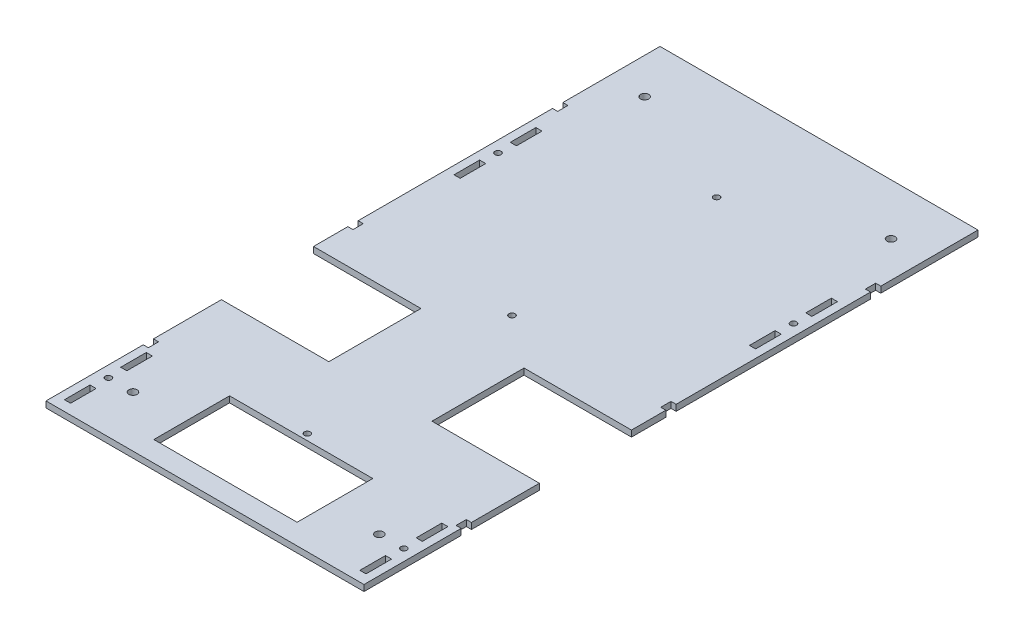
SolidWorks part; units mm, degrees
material "PMMA"
ref_plane "Front Plane" through (0, 0, 0) normal (0, 0, 1) x (1, 0, 0)
ref_plane "Top Plane" through (0, 0, 0) normal (0, 1, 0) x (1, 0, 0)
ref_plane "Right Plane" through (0, 0, 0) normal (1, 0, 0) x (0, 0, -1)
sketch "Schizzo1" plane through (0, 0, 0) normal (0, 1, 0) x (1, 0, 0)
  line L0 (-80.18, 150) -> (80.18, -150) construction
  line L1 (-80.18, 150) -> (80.18, 150)
  line L2 (-80.18, 150) -> (-80.18, -150)
  line L3 (-80.18, -150) -> (80.18, -150)
  line L4 (80.18, 150) -> (80.18, -150)
  point P4 (0, 0)
  dimension "D1" = 300
  dimension "D2" = 160.36
extrude "Estrusione-Estrusione1" add sketch "Schizzo1" along normal blind 3
sketch "Schizzo3" plane through (0, 0, 0) normal (0, 1, 0) x (1, 0, 0)
  line L0 (-80.18, 0) -> (80.18, 0) construction
  line L1 (-80.18, 150) -> (-80.18, -150) construction
  line L2 (0, 0) -> (0, -100) construction
  line L3 (0, 150) -> (0, -150) construction
  line L4 (80.18, 150) -> (-80.18, 150) construction
  line L5 (-80.18, -150) -> (80.18, -150) construction
  line L6 (0, 0) -> (0, 100) construction
  line L7 (-75.18, -97.5) -> (-80.18, -97.5)
  line L8 (-75.18, -2.5) -> (-80.18, -2.5)
  line L9 (-75.18, -2.5) -> (-75.18, 2.5)
  line L10 (-75.18, 2.5) -> (-80.18, 2.5)
  line L11 (-80.18, -2.5) -> (-80.18, 2.5)
  line L12 (-80.18, -102.5) -> (-80.18, -97.5)
  line L13 (-75.18, -102.5) -> (-80.18, -102.5)
  line L14 (-75.18, -102.5) -> (-75.18, -97.5)
  line L15 (-75.18, 2.5) -> (-75.18, -97.5) construction
  line L16 (-75.18, 97.5) -> (-80.18, 97.5)
  line L17 (-80.18, 97.5) -> (-80.18, 102.5)
  line L18 (-75.18, 102.5) -> (-80.18, 102.5)
  line L19 (-75.18, 97.5) -> (-75.18, 102.5)
  line L20 (-75.18, -2.5) -> (-75.18, 97.5) construction
  line L21 (75.18, -102.5) -> (75.18, -97.5)
  line L22 (75.18, -97.5) -> (80.18, -97.5)
  line L23 (80.18, -102.5) -> (80.18, -97.5)
  line L24 (75.18, -102.5) -> (80.18, -102.5)
  line L25 (75.18, -2.5) -> (75.18, 2.5)
  line L26 (75.18, 2.5) -> (80.18, 2.5)
  line L27 (80.18, -2.5) -> (80.18, 2.5)
  line L28 (75.18, -2.5) -> (80.18, -2.5)
  line L29 (75.18, 97.5) -> (75.18, 102.5)
  line L30 (75.18, 102.5) -> (80.18, 102.5)
  line L31 (80.18, 97.5) -> (80.18, 102.5)
  line L32 (75.18, 97.5) -> (80.18, 97.5)
  line L33 (-80.18, 150) -> (-80.18, -150) construction
  line L34 (-80.18, -19.3) -> (-25.18, -19.3)
  line L35 (-80.18, -19.3) -> (-80.18, -64.3)
  line L36 (-80.18, -64.3) -> (-25.18, -64.3)
  line L37 (-25.18, -19.3) -> (-25.18, -64.3)
  line L38 (80.18, -19.3) -> (80.18, -64.3)
  line L39 (80.18, -64.3) -> (25.18, -64.3)
  line L40 (25.18, -19.3) -> (25.18, -64.3)
  line L41 (80.18, -19.3) -> (25.18, -19.3)
  line L54 (80.18, -150) -> (80.18, 150) construction
  circle A0 centre (0, 0) radius 1.5
  circle A1 centre (0, -100) radius 1.5
  circle A2 centre (0, 100) radius 1.5
  circle A8 centre (-5.0427, -204.0432) radius 1.5
  point P24 (-80.18, 0)
  dimension "D1" = 3
  dimension "D2" = 100
  dimension "D4" = 100
  dimension "D5" = 5
  dimension "D6" = 5
  dimension "D7" = 100
  dimension "D9" = 100
  dimension "D11" = 55
  dimension "D12" = 45
  dimension "D13" = 16.8
  dimension "D10" = 2
extrude "Taglio-Estrusione1" cut sketch "Schizzo3" along direction (0, 1, 0) on the side of the normal through all
sketch "Schizzo4" plane through (0, 0, 0) normal (0, 1, 0) x (1, 0, 0)
  line L0 (-80.18, -102.5) -> (-80.18, -150) construction
  line L1 (-80.18, -150) -> (80.18, -150) construction
  line L2 (0, -150) -> (0, 150) construction
  line L3 (80.18, 150) -> (-80.18, 150) construction
  line L4 (75.18, 0) -> (-75.18, 0) construction
  line L5 (75.18, 2.5) -> (75.18, -2.5) construction
  line L6 (-75.18, -2.5) -> (-75.18, 2.5) construction
  circle A0 centre (-60.18, -125) radius 2
  circle A1 centre (60.18, -125) radius 2
  circle A2 centre (-60.18, 125) radius 2
  circle A3 centre (60.18, 125) radius 2
  dimension "D1" = 4
  dimension "D2" = 20
  dimension "D3" = 25
  dimension "D4" = 250
  dimension "D5" = 120.36
extrude "Taglio-Estrusione2" cut sketch "Schizzo4" along direction (0, 1, 0) on the side of the normal through all
sketch "Schizzo5" plane through (0, 0, 0) normal (0, 1, 0) x (1, 0, 0)
  line L0 (0, -150) -> (0, 150) construction
  line L1 (-80.18, -150) -> (80.18, -150) construction
  line L2 (80.18, 150) -> (-80.18, 150) construction
  line L3 (-80.18, -125) -> (80.18, -125) construction
  line L5 (80.18, -150) -> (80.18, -102.5) construction
  line L6 (-80.18, 65.35) -> (80.18, 65.35) construction
  line L7 (-80.18, 97.5) -> (-80.18, 2.5) construction
  line L8 (80.18, 2.5) -> (80.18, 97.5) construction
  line L10 (-80.18, 150) -> (-80.18, -19.3) construction
  line L11 (-80.18, -64.3) -> (-80.18, -150) construction
  line L12 (72.18, 72.85) -> (72.18, 57.85) construction
  line L13 (70.68, 85.35) -> (73.68, 85.35)
  line L14 (70.68, 85.35) -> (70.68, 72.85)
  line L15 (70.68, 72.85) -> (73.68, 72.85)
  line L16 (73.68, 85.35) -> (73.68, 72.85)
  line L17 (70.68, 57.85) -> (73.68, 57.85)
  line L18 (70.68, 57.85) -> (70.68, 45.35)
  line L19 (70.68, 45.35) -> (73.68, 45.35)
  line L20 (73.68, 57.85) -> (73.68, 45.35)
  line L21 (-70.68, 57.85) -> (-73.68, 57.85)
  line L22 (-70.68, 57.85) -> (-70.68, 45.35)
  line L23 (-70.68, 45.35) -> (-73.68, 45.35)
  line L24 (-73.68, 57.85) -> (-73.68, 45.35)
  line L25 (-70.68, 85.35) -> (-73.68, 85.35)
  line L26 (-70.68, 85.35) -> (-70.68, 72.85)
  line L27 (-70.68, 72.85) -> (-73.68, 72.85)
  line L28 (-73.68, 85.35) -> (-73.68, 72.85)
  line L29 (72.18, -117.5) -> (72.18, -132.5) construction
  line L30 (70.68, -105) -> (73.68, -105)
  line L31 (70.68, -105) -> (70.68, -117.5)
  line L32 (70.68, -117.5) -> (73.68, -117.5)
  line L33 (73.68, -105) -> (73.68, -117.5)
  line L34 (70.68, -132.5) -> (73.68, -132.5)
  line L35 (70.68, -132.5) -> (70.68, -145)
  line L36 (70.68, -145) -> (73.68, -145)
  line L37 (73.68, -132.5) -> (73.68, -145)
  line L38 (-70.68, -105) -> (-73.68, -105)
  line L39 (-70.68, -105) -> (-70.68, -117.5)
  line L40 (-70.68, -117.5) -> (-73.68, -117.5)
  line L41 (-73.68, -105) -> (-73.68, -117.5)
  line L42 (-70.68, -132.5) -> (-73.68, -132.5)
  line L43 (-70.68, -132.5) -> (-70.68, -145)
  line L44 (-70.68, -145) -> (-73.68, -145)
  line L45 (-73.68, -132.5) -> (-73.68, -145)
  circle A0 centre (72.18, 65.35) radius 1.5
  circle A1 centre (-72.18, 65.35) radius 1.5
  circle A2 centre (72.18, -125) radius 1.5
  circle A3 centre (-72.18, -125) radius 1.5
  dimension "D4" = 3
  dimension "D9" = 3
  dimension "D1" = 12.5
  dimension "D2" = 3
  dimension "D3" = 40
  dimension "D5" = 6.5
  dimension "D6" = 12.5
  dimension "D7" = 3
  dimension "D8" = 40
  dimension "D10" = 6.5
  dimension "D11" = 25
extrude "Taglio-Estrusione3" cut sketch "Schizzo5" along direction (0, 1, 0) on the side of the normal through all
sketch "Schizzo6" plane through (0, 0, 0) normal (0, 1, 0) x (1, 0, 0)
  line L1 (35, -140) -> (-35, -140)
  line L2 (35, -140) -> (35, -103)
  line L3 (35, -103) -> (-35, -103)
  line L4 (-35, -140) -> (-35, -103)
  line L6 (-80.18, -150) -> (80.18, -150) construction
  dimension "D1" = 37
  dimension "D2" = 70
  dimension "D3" = 35
  dimension "D4" = 10
extrude "Taglio-Estrusione4" cut sketch "Schizzo6" along direction (0, 1, 0) on the side of the normal through all
sketch "Schizzo7" plane through (0, 3, 0) normal (0, 1, 0) x (1, 0, 0)
  line L0 (-75.18, 102.5) -> (-80.18, 102.5) construction
  line L1 (-80.18, 150) -> (-77.68, 150)
  line L2 (-80.18, 150) -> (-80.18, 102.5)
  line L3 (-80.18, 102.5) -> (-77.68, 102.5)
  line L4 (-77.68, 150) -> (-77.68, 102.5)
  line L5 (-75.18, 2.5) -> (-80.18, 2.5) construction
  line L6 (-77.68, 2.5) -> (-80.18, 2.5)
  line L7 (-77.68, 2.5) -> (-77.68, 97.5)
  line L8 (-77.68, 97.5) -> (-80.18, 97.5)
  line L9 (-80.18, 2.5) -> (-80.18, 97.5)
  line L10 (-80.18, -2.5) -> (-75.18, -2.5) construction
  line L11 (-77.68, -2.5) -> (-80.18, -2.5)
  line L12 (-77.68, -2.5) -> (-77.68, -19.3)
  line L13 (-77.68, -19.3) -> (-80.18, -19.3)
  line L14 (-80.18, -2.5) -> (-80.18, -19.3)
  line L15 (-75.18, -97.5) -> (-80.18, -97.5) construction
  line L16 (-80.18, -64.3) -> (-77.68, -64.3)
  line L17 (-80.18, -64.3) -> (-80.18, -97.5)
  line L18 (-80.18, -97.5) -> (-77.68, -97.5)
  line L19 (-77.68, -64.3) -> (-77.68, -97.5)
  line L20 (-80.18, -150) -> (80.18, -150) construction
  line L21 (-77.68, -150) -> (-80.18, -150)
  line L22 (-77.68, -150) -> (-77.68, -102.5)
  line L23 (-77.68, -102.5) -> (-80.18, -102.5)
  line L24 (-80.18, -150) -> (-80.18, -102.5)
  line L25 (75.18, -102.5) -> (80.18, -102.5) construction
  line L26 (80.18, -150) -> (77.68, -150)
  line L27 (80.18, -150) -> (80.18, -102.5)
  line L28 (80.18, -102.5) -> (77.68, -102.5)
  line L29 (77.68, -150) -> (77.68, -102.5)
  line L30 (80.18, -97.5) -> (75.18, -97.5) construction
  line L31 (80.18, -64.3) -> (77.68, -64.3)
  line L32 (80.18, -64.3) -> (80.18, -97.5)
  line L33 (80.18, -97.5) -> (77.68, -97.5)
  line L34 (77.68, -64.3) -> (77.68, -97.5)
  line L35 (75.18, -2.5) -> (80.18, -2.5) construction
  line L36 (80.18, -19.3) -> (77.68, -19.3)
  line L37 (80.18, -19.3) -> (80.18, -2.5)
  line L38 (80.18, -2.5) -> (77.68, -2.5)
  line L39 (77.68, -19.3) -> (77.68, -2.5)
  line L40 (80.18, 102.5) -> (75.18, 102.5) construction
  line L41 (80.18, 150) -> (77.68, 150)
  line L42 (80.18, 150) -> (80.18, 102.5)
  line L43 (80.18, 102.5) -> (77.68, 102.5)
  line L44 (77.68, 150) -> (77.68, 102.5)
  line L45 (80.18, 2.5) -> (75.18, 2.5) construction
  line L46 (80.18, 97.5) -> (77.68, 97.5)
  line L47 (80.18, 97.5) -> (80.18, 2.5)
  line L48 (80.18, 2.5) -> (77.68, 2.5)
  line L49 (77.68, 97.5) -> (77.68, 2.5)
extrude "Taglio-Estrusione5" cut sketch "Schizzo7" against normal through all
equation "\"Thickness2\"=12"
equation "\"Thickness3\"=3"
equation "\"D1@Estrusione-Estrusione1\"=\"Thickness3\""
equation "\"D5@Schizzo3\"=\"Thickness5\""
equation "\"D6@Schizzo3\"=\"Thickness5\""
equation "\"Thickness5\"= 5"
equation "\"D2@Schizzo5\"=\"Thickness3\""
equation "\"D7@Schizzo5\"=\"Thickness3\""
